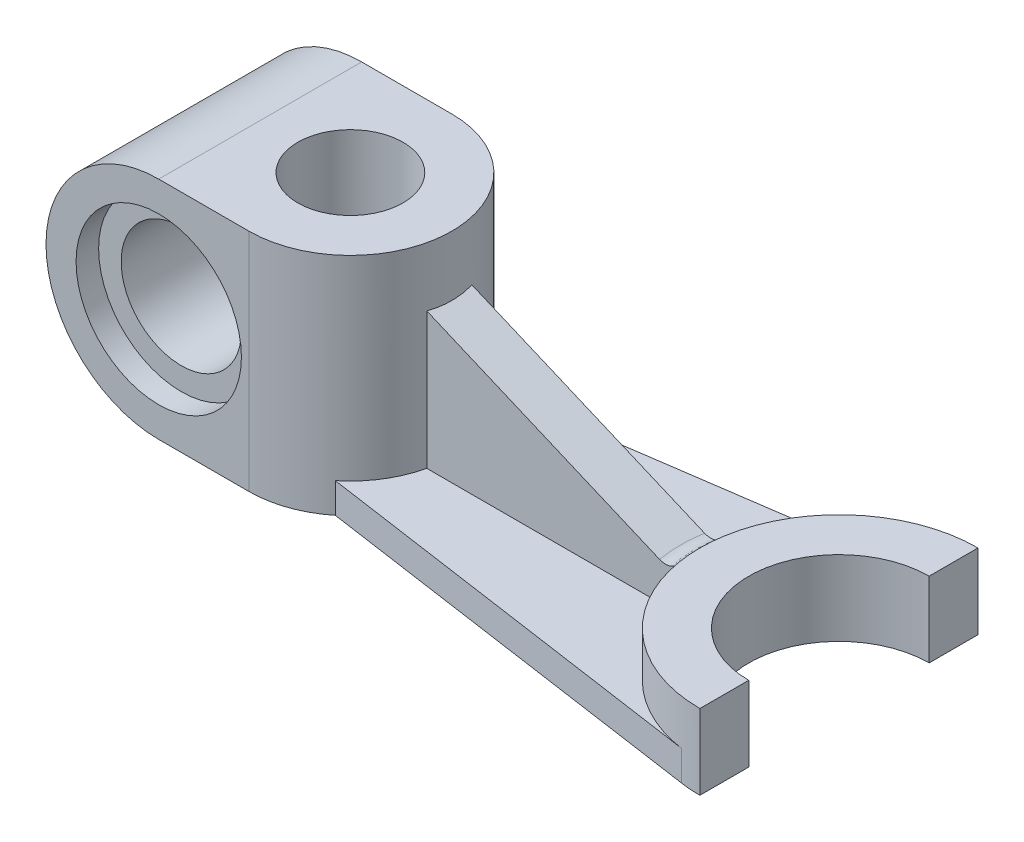
SolidWorks part; units mm, degrees
note: The reader was unsure of these and kept them because the rebuilt part matched: shared geometry of "Sketch9<3>".
ref_plane "Front Plane" through (0, 0, 0) normal (0, 0, 1) x (1, 0, 0)
ref_plane "Top Plane" through (0, 0, 0) normal (0, 1, 0) x (1, 0, 0)
ref_plane "Right Plane" through (0, 0, 0) normal (1, 0, 0) x (0, 0, -1)
sketch "Sketch2" plane through (0, 0, 0) normal (0, 1, 0) x (1, 0, 0)
  line L0 (-19.05, 21.4313) -> (-19.05, -21.4313)
  line L1 (-19.05, 21.4313) -> (0, 21.4313)
  line L2 (-19.05, -21.4313) -> (0, -21.4313)
  circle A0 centre (0, 0) radius 11.1125
  arc A2 (0, 21.4313) -> (0, -21.4313) centre (0, 0) cw
  point P7 (14.6435, -15.6482)
  dimension "D1" = 22.225
  dimension "D2" = 19.05
  dimension "D4" = 21.4313
  dimension "D3" = 42.8625
  dimension "D5" = 15.6482
extrude "Boss-Extrude2" add sketch "Sketch2" along normal blind 47.625
sketch "Sketch4" plane through (0, 0, 0) normal (0, 1, 0) x (1, 0, 0)
  line L0 (0, 0) -> (81.9902, 0) construction
  line L1 (103.1875, 29.3687) -> (103.1875, 19.05)
  line L2 (103.1875, -19.05) -> (103.1875, -29.3687)
  arc A0 (103.1875, 19.05) -> (103.1875, -19.05) centre (103.1875, 0) ccw
  arc A1 (103.1875, 29.3687) -> (103.1875, -29.3687) centre (103.1875, 0) ccw
  dimension "D1" = 38.1
  dimension "D2" = 58.7375
  dimension "D3" = 103.1875
extrude "Boss-Extrude3" add sketch "Sketch4" along normal blind 15.875 separate body
sketch "Sketch5" plane through (0, 0, 0) normal (0, 1, 0) x (1, 0, 0)
  line L0 (13.4704, -16.6687) -> (98.9737, -29.0649)
  line L2 (-27.0176, 0) -> (131.5103, 0) construction
  line L5 (13.4704, 16.6687) -> (98.9737, 29.0649)
  arc A3 (103.1875, 29.3687) -> (103.1875, -29.3687) centre (103.1875, 0) ccw construction
  arc A4 (103.1875, 29.3687) -> (103.1875, -29.3687) centre (103.1875, 0) ccw construction
  arc A5 (98.9737, 29.0649) -> (98.9737, -29.0649) centre (103.1875, 0) ccw
  arc A8 (0, -21.4313) -> (0, 21.4313) centre (0, 0) ccw construction
  arc A9 (0, -21.4313) -> (0, 21.4313) centre (0, 0) ccw construction
  arc A10 (13.4704, -16.6687) -> (13.4704, 16.6687) centre (0, 0) ccw
  point P26 (13.4704, -16.6687)
  dimension "D1" = 16.6687
extrude "Boss-Extrude6" add sketch "Sketch5" along normal blind 6.35
sketch "Sketch7" plane through (0, 0, 0) normal (0, 0, 1) x (1, 0, 0)
  line L0 (-42.8625, 0) -> (-42.8625, 47.625) construction
  line L1 (0, 47.625) -> (0, 0) construction
  line L2 (0, 23.8125) -> (-71.9809, 23.8125) construction
  line L3 (-19.05, 47.625) -> (-19.05, 0) construction
  line L4 (-19.05, 47.625) -> (-19.05, 0)
  arc A0 (-19.05, 47.625) -> (-19.05, 0) centre (-19.05, 23.8125) ccw
  point P6 (-42.8625, 23.8125)
  dimension "D1" = 42.8625
extrude "Boss-Extrude7" add sketch "Sketch7" along normal mid plane 42.8625
ref_plane "Plane1" through (0, 0, 0) normal (0, 0, 1) x (1, 0, 0)
sketch "Sketch9" plane through (0, 0, 0) normal (0, 0, 1) x (1, 0, 0)
  line L0 (0, 0) -> (0, 59.4727) construction
  line L1 (-46.9447, 23.8125) -> (37.9418, 23.8125) construction
  line L2 (-19.05, 56.3218) -> (-19.05, -2.8204) construction
  circle A0 centre (-19.05, 23.8125) radius 12.7
  circle A1 centre (-19.05, 23.8125) radius 17.4625
  point P8 (-19.05, 23.8125)
  dimension "D2" = 34.925
  dimension "D3" = 25.4
  dimension "D1" = 23.8125
extrude "Cut-Extrude4" cut sketch "Sketch9" against normal through all both and the other way through all contours A0
extrude "Cut-Extrude5" cut sketch "Sketch9<3>" against normal blind 4.7625 from vertex contours A1 A0
sketch "Sketch9<3>" plane through (0, 0, 0) normal (0, 0, 1) x (1, 0, 0) same geometry as "Sketch9"
sketch "Sketch11" plane through (0, 0, 0) normal (0, 0, 1) x (1, 0, 0)
  line L0 (73.8188, 15.875) -> (73.8188, 6.35) construction
  line L1 (21.4313, 47.625) -> (0, 47.625) construction
  line L2 (103.1875, 15.875) -> (73.8188, 15.875) construction
  line L5 (21.4313, 6.35) -> (21.4313, 47.625) construction
  line L6 (21.4313, 34.925) -> (73.8188, 12.7)
  point P1 (73.8188, 12.7)
  point P8 (21.4313, 34.925)
  dimension "D1" = 3.175
  dimension "D2" = 12.7
rib "Rib1" sketch "Sketch11" sketch "Sketch11" thickness 9.525 extrusion direction parallel to sketch draft on no parameters "D1"=9.525
fillet "Fillet1" radius 3.175 1 edges at (73.8188, 12.7, 0)
